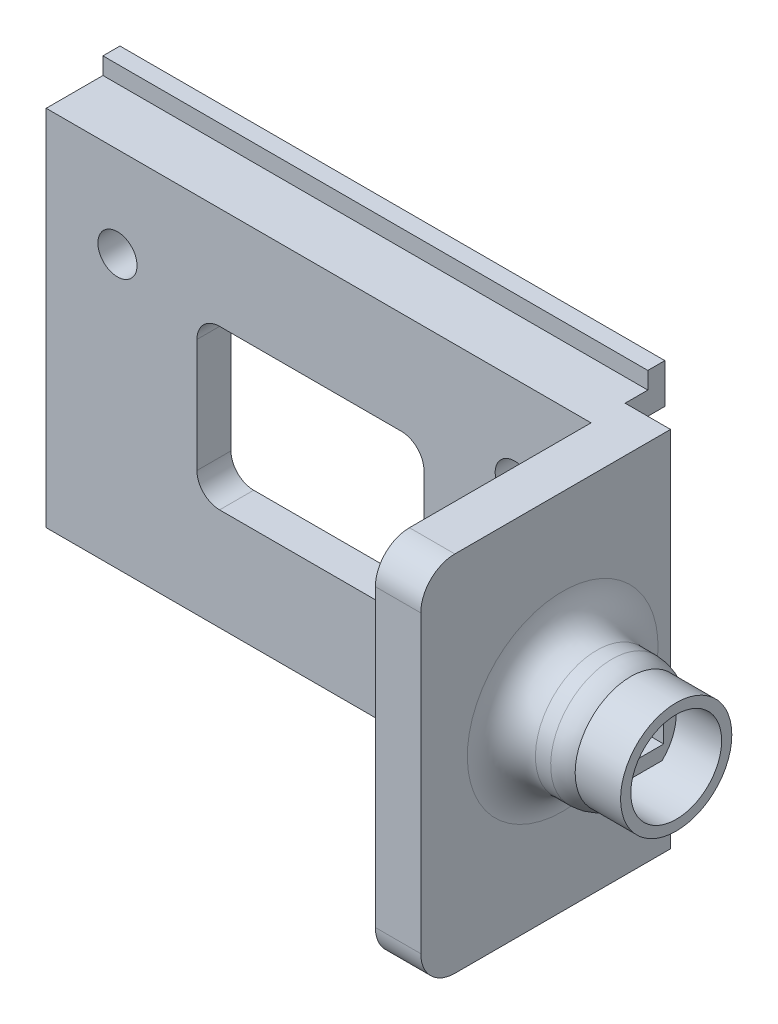
SolidWorks part; units mm, degrees
ref_plane "Front Plane" through (0, 0, 0) normal (0, 0, 1) x (1, 0, 0)
ref_plane "Top Plane" through (0, 0, 0) normal (0, 1, 0) x (1, 0, 0)
ref_plane "Right Plane" through (0, 0, 0) normal (1, 0, 0) x (0, 0, -1)
sketch "Sketch1" plane through (0, 0, 0) normal (0, 0, 1) x (1, 0, 0)
  line L1 (0, 0) -> (52, 0)
  line L2 (0, 0) -> (0, -32)
  line L3 (0, -32) -> (52, -32)
  line L4 (52, 0) -> (52, -32)
  dimension "D1" = 52
  dimension "D2" = 32
extrude "Boss-Extrude1" add sketch "Sketch1" along normal blind 3
ref_plane "Plane1" through (0, 0, 2) normal (0, 0, -1) x (-1, 0, 0)
sketch "Sketch2" plane through (0, 0, 2) normal (0, 0, -1) x (-1, 0, 0)
  line L1 (-48, 0) -> (-52, 0)
  line L2 (-48, 0) -> (-48, -32)
  line L3 (-48, -32) -> (-52, -32)
  line L4 (-52, 0) -> (-52, -32)
  dimension "D1" = 4
extrude "Boss-Extrude2" add sketch "Sketch2" against normal blind 20
fillet "Fillet1" radius 3 2 edges at (50, -32, 22) (50, 0, 22)
sketch "Sketch4" plane through (0, 0, 3) normal (0, 0, 1) x (1, 0, 0)
  line L0 (48, 0) -> (0, 0) construction
  circle A0 centre (41.2777, -8) radius 1.725
  circle A1 centre (6.2777, -8) radius 1.725
  dimension "D1" = 35
  dimension "D2" = 8
  dimension "D3" = 8
extrude "Cut-Extrude2" cut sketch "Sketch4" against normal up to surface (3 mm away) up to face at (26, -16, 0)
sketch "Sketch6" plane through (0, 0, 3) normal (0, 0, 1) x (1, 0, 0)
  line L0 (48, 0) -> (0, 0) construction
  line L1 (33.2777, -9) -> (13.2777, -9)
  line L2 (33.2777, -9) -> (33.2777, -23)
  line L3 (33.2777, -23) -> (13.2777, -23)
  line L4 (13.2777, -9) -> (13.2777, -23)
  circle A0 centre (6.2777, -8) radius 1.725 construction
  dimension "D3" = 7
  dimension "D1" = 14
  dimension "D2" = 20
  dimension "D4" = 9
extrude "Cut-Extrude3" cut sketch "Sketch6" against normal up to surface (3 mm away) up to face at (43.0027, -8, 0)
sketch "Sketch7" plane through (52, 0, 0) normal (1, 0, 0) x (0, 0, -1)
  line L0 (-22, -16) -> (2.0181, -16) construction
  line L1 (-12.4, -17.7) -> (-6.6, -17.7)
  line L2 (-12.4, -17.7) -> (-12.4, -14.3)
  line L3 (-12.4, -14.3) -> (-6.6, -14.3)
  line L4 (-6.6, -17.7) -> (-6.6, -14.3)
  line L5 (-22, -3) -> (-22, -29) construction
  line L6 (-9.5, -32) -> (-9.5, 5.4647) construction
  line L7 (-19, -32) -> (0, -32) construction
  line L8 (-13.6, -13.1) -> (-5.4, -13.1)
  line L9 (-5.4, -18.9) -> (-5.4, -13.1)
  line L10 (-13.6, -18.9) -> (-5.4, -18.9)
  line L11 (-13.6, -18.9) -> (-13.6, -13.1)
  dimension "D5" = 1.2
  dimension "D1" = 5.8
  dimension "D2" = 3.4
  dimension "D3" = 1.7
  dimension "D4" = 2.9
sketch "Sketch8" plane through (52, 0, 0) normal (1, 0, 0) x (0, 0, -1)
  line L0 (-9.5, -16) -> (-9.5, 10.2333) construction
  line L1 (-22, -16) -> (3, -16) construction
  line L3 (0, -32) -> (0, 0) construction
  line L6 (-19, -32) -> (0, -32) construction
  circle A0 centre (-9.5, -16) radius 4.25
  circle A1 centre (-9.5, -16) radius 5.4
  dimension "D1" = 10.8
  dimension "D2" = 8.5
  dimension "D3" = 9.5
  dimension "D4" = 16
extrude "Boss-Extrude4" add sketch "Sketch7" along normal blind 6
sketch "Sketch10" plane through (52, 0, 0) normal (1, 0, 0) x (0, 0, -1)
  line L0 (-19, -32) -> (0, -32) construction
  line L1 (0, -32) -> (0, 0) construction
  circle A0 centre (-9.5, -16) radius 4
  circle A1 centre (-9.5, -16) radius 4.9
  dimension "D1" = 9.8
  dimension "D2" = 8
  dimension "D3" = 16
  dimension "D4" = 9.5
extrude "Boss-Extrude6" add sketch "Sketch10" along normal blind 10
extrude "Boss-Extrude5" add sketch "Sketch8" along normal blind 6
fillet "Fillet2" radius 2 4 edges at (13.2777, -9, 1.5) (13.2777, -23, 1.5) (33.2777, -9, 1.5) (33.2777, -23, 1.5)
fillet "Fillet3" radius 3 2 edges at (52, -21.4, 9.5) (58, -16, 4.1)
sketch "Sketch15" plane through (0, 0, 0) normal (-1, 0, 0) x (0, 0, 1)
  line L1 (3, -32) -> (0, -32) construction
  line L6 (-3.5, -2) -> (-3.5, 1.5)
  line L8 (0, -16) -> (-8.2188, -16) construction
  line L9 (0, 0) -> (0, -32) construction
  line L17 (0, -2) -> (-3.5, -2)
  line L23 (-3.5, -33.5) -> (-2, -33.5)
  line L24 (-3.5, -30) -> (-3.5, -33.5)
  line L25 (0, -30) -> (-3.5, -30)
  line L26 (0, -32) -> (0, -30)
  line L27 (-2, -32) -> (0, -32)
  line L28 (-2, -33.5) -> (-2, -32)
  line L29 (0, 0) -> (0, -2)
  line L30 (-2, 0) -> (0, 0)
  line L31 (-2, 1.5) -> (-2, 0)
  line L32 (-3.5, 1.5) -> (-2, 1.5)
  dimension "D1" = 2
  dimension "D2" = 2
  dimension "D3" = 3.5
extrude "Boss-Extrude7" add sketch "Sketch15" against normal up to surface (48 mm away) up to face at (48, -16, 14.8738)
